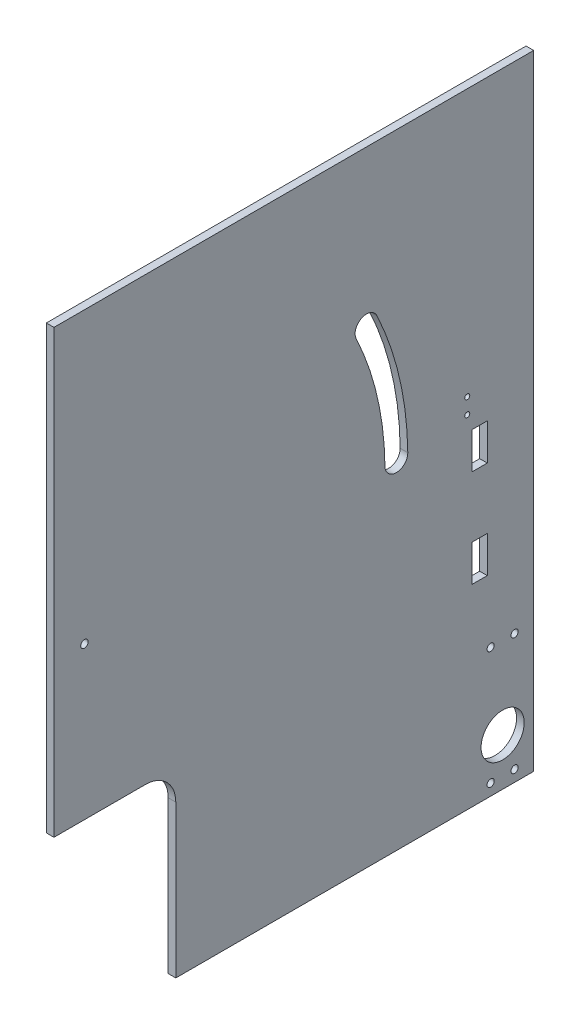
SolidWorks part; units mm, degrees
material "Acrylic (Medium-high impact)"
ref_plane "Front" through (0, 0, 0) normal (0, 0, 1) x (1, 0, 0)
ref_plane "Top" through (0, 0, 0) normal (0, 1, 0) x (1, 0, 0)
ref_plane "Right" through (0, 0, 0) normal (1, 0, 0) x (0, 0, -1)
sketch "Sketch1" plane through (0, 0, 0) normal (1, 0, 0) x (0, 0, -1)
  line L1 (-100.0125, 130.175) -> (100.0125, 130.175)
  line L2 (-100.0125, 130.175) -> (-100.0125, -130.175)
  line L3 (-100.0125, -130.175) -> (100.0125, -130.175)
  line L4 (100.0125, 130.175) -> (100.0125, -130.175)
  point P4 (-100.0125, 0)
  point P6 (0, 130.175)
  dimension "D1" = 260.35
  dimension "D2" = 200.025
extrude "Boss-Extrude1" add sketch "Sketch1" along normal blind 3.175
sketch "Sketch3" plane through (0, 0, 0) normal (-1, 0, 0) x (0, 0, 1)
  line L0 (-55.5625, 104.775) -> (77.7875, 104.775)
  line L1 (77.7875, 79.375) -> (-55.5625, 79.375)
  line L2 (-26.9875, 130.175) -> (-26.9875, -130.175) construction
  line L3 (-100.0125, 130.175) -> (100.0125, 130.175) construction
  line L4 (100.0125, -130.175) -> (-100.0125, -130.175) construction
  line L5 (100.0125, 130.175) -> (100.0125, -130.175) construction
  line L6 (-60.7375, 79.375) -> (-60.7375, 80.4772)
  line L12 (-55.5625, 92.075) -> (-68.2625, 92.075) construction
  arc A0 (77.7875, 104.775) -> (77.7875, 79.375) centre (77.7875, 92.075) cw
  arc A1 (-55.5625, 79.375) -> (-55.5625, 104.775) centre (-55.5625, 92.075) cw
  point P15 (90.4875, 92.075)
  dimension "D1" = 25.4
  dimension "D3" = 133.35
  dimension "D2" = 9.525
  dimension "D4" = 127
  dimension "D5" = 222.25
  dimension "D8" = 5.175
extrude "Cut-Extrude1" [suppressed] cut sketch "Sketch3" against normal through all contours A1 L1 A0 L0
sketch "Sketch6" plane through (3.175, 0, 0) normal (1, 0, 0) x (0, 0, -1)
  line L0 (117.5875, -88.265) -> (117.5875, -83.185)
  line L1 (139.5875, -83.185) -> (139.5875, -88.265)
  line L2 (111.5875, -103.765) -> (111.5875, -98.685)
  line L3 (114.5875, -103.765) -> (114.5875, -98.685)
  line L4 (111.5875, -72.765) -> (111.5875, -67.685)
  line L5 (114.5875, -72.765) -> (114.5875, -67.685)
  line L6 (128.5875, -83.185) -> (128.5875, -88.265) construction
  line L7 (145.5875, -103.765) -> (145.5875, -98.685)
  line L8 (142.5875, -103.765) -> (142.5875, -98.685)
  line L9 (142.5875, -72.765) -> (142.5875, -67.685)
  line L10 (145.5875, -72.765) -> (145.5875, -67.685)
  line L11 (-100.0125, 130.175) -> (-100.0125, -130.175) construction
  line L12 (-100.0125, -130.175) -> (100.0125, -130.175) construction
  arc A0 (117.5875, -88.265) -> (139.5875, -88.265) centre (128.5875, -88.265) ccw
  arc A1 (139.5875, -83.185) -> (117.5875, -83.185) centre (128.5875, -83.185) ccw
  arc A2 (111.5875, -103.765) -> (114.5875, -103.765) centre (113.0875, -103.765) ccw
  arc A3 (114.5875, -98.685) -> (111.5875, -98.685) centre (113.0875, -98.685) ccw
  arc A4 (111.5875, -72.765) -> (114.5875, -72.765) centre (113.0875, -72.765) ccw
  arc A5 (114.5875, -67.685) -> (111.5875, -67.685) centre (113.0875, -67.685) ccw
  arc A6 (145.5875, -103.765) -> (142.5875, -103.765) centre (144.0875, -103.765) cw
  arc A7 (142.5875, -98.685) -> (145.5875, -98.685) centre (144.0875, -98.685) cw
  arc A8 (145.5875, -72.765) -> (142.5875, -72.765) centre (144.0875, -72.765) cw
  arc A9 (142.5875, -67.685) -> (145.5875, -67.685) centre (144.0875, -67.685) cw
  circle A10 centre (113.0875, -69.36) radius 3.175
  circle A11 centre (144.0875, -69.36) radius 3.175
  circle A12 centre (113.0875, -102.09) radius 3.175
  circle A13 centre (144.0875, -102.09) radius 3.175
  point P37 (128.5875, -85.725)
  point P38 (139.5875, -85.725)
  dimension "D5" = 1.5
  dimension "D9" = 1.5
  dimension "D12" = 6.35
  dimension "D1" = 5.08
  dimension "D2" = 5.08
  dimension "D3" = 15.5
  dimension "D4" = 15.5
  dimension "D6" = 15.5
  dimension "D7" = 15.5
  dimension "D8" = 5.08
  dimension "D10" = 228.6
  dimension "D11" = 44.45
sketch "Sketch8" plane through (0, 0, 0) normal (-1, 0, 0) x (0, 0, 1)
  line L0 (100.0125, 130.175) -> (100.0125, -130.175) construction
  line L1 (100.0125, -130.175) -> (-100.0125, -130.175) construction
  line L3 (100.0125, -130.175) -> (-100.0125, -130.175) construction
  circle A0 centre (87.3125, 9.525) radius 1.55
  circle A5 centre (-72.3175, 18.925) radius 1.05
  circle A6 centre (-72.3175, 12.425) radius 1.05
  point P11 (-63.8175, 22.225)
  dimension "D1" = 3.1
  dimension "D15" = 3.3
  dimension "D8" = 2.1
  dimension "D2" = 12.7
  dimension "D3" = 139.7
  dimension "D6" = 151.13
  dimension "D7" = 152.4
  dimension "D9" = 6.5
  dimension "D12" = 8.5
extrude "Cut-Extrude7" cut sketch "Sketch8" against normal through all
sketch "Sketch9" plane through (0, 0, 0) normal (-1, 0, 0) x (0, 0, 1)
  line L0 (100.0125, 130.175) -> (100.0125, -130.175) construction
  line L1 (100.0125, -53.975) -> (49.2125, -53.975)
  line L2 (100.0125, -53.975) -> (100.0125, -130.175)
  line L3 (100.0125, -130.175) -> (49.2125, -130.175)
  line L4 (49.2125, -53.975) -> (49.2125, -130.175)
  line L5 (100.0125, -130.175) -> (-100.0125, -130.175) construction
  dimension "D1" = 50.8
  dimension "D2" = 76.2
extrude "Cut-Extrude8" cut sketch "Sketch9" against normal through all
fillet "Fillet1" radius 12.7 1 edges at (1.5875, -53.975, 49.2125)
sketch "Sketch10" plane through (0, 0, 0) normal (-1, 0, 0) x (0, 0, 1)
  line L4 (-42.8232, -130.175) -> (-42.8232, 6.325) construction
  line L5 (49.2125, -130.175) -> (-100.0125, -130.175) construction
  arc A9 (-28.2913, 69.3688) -> (-42.8232, 6.325) centre (87.3125, 9.525) ccw construction
  arc A10 (-34.6312, 67.0954) -> (-47.5281, 11.1443) centre (87.3125, 9.525) ccw
  arc A11 (-26.0179, 63.0289) -> (-38.0038, 11.03) centre (87.3125, 9.525) ccw
  arc A12 (-47.5281, 11.1443) -> (-38.0038, 11.03) centre (-42.766, 11.0872) ccw
  arc A13 (-34.6312, 67.0954) -> (-26.0179, 63.0289) centre (-30.3245, 65.0622) cw
  circle A14 centre (87.3125, 9.525) radius 125.3254 construction
  circle A15 centre (87.3125, 9.525) radius 130.175 construction
  circle A16 centre (87.3125, 9.525) radius 134.8504 construction
  point P23 (-28.2913, 69.3688)
  dimension "D1" = 4.7625
  dimension "D2" = 136.5
  dimension "D4" = 260.35
  dimension "D3" = 53.975
extrude "Cut-Extrude9" cut sketch "Sketch10" against normal through all
sketch "Sketch14" plane through (3.175, 0, 0) normal (1, 0, 0) x (0, 0, -1)
  line L0 (36.5125, -130.175) -> (36.5125, 130.175) construction
  line L5 (-49.2125, -130.175) -> (100.0125, -130.175) construction
  line L6 (100.0125, 130.175) -> (-100.0125, 130.175) construction
  line L7 (-100.0125, 130.175) -> (-100.0125, -53.975) construction
  line L14 (65.0875, -120.523) -> (65.0875, -126.873) construction
  circle A0 centre (-87.3125, 9.525) radius 186.3916 construction
  arc A1 (35.0388, -128.905) -> (41.3847, -122.7825) centre (35.0388, -122.555) ccw construction
  circle A2 centre (65.0875, -126.873) radius 1.5
  circle A3 centre (65.0875, -120.523) radius 1.5
  dimension "D6" = 3
  dimension "D7" = 6.35
  dimension "D1" = 136.525
  dimension "D8" = 3.302
  dimension "D9" = 28.575
extrude "Cut-Extrude11" [suppressed] cut sketch "Sketch14" against normal through all
sketch "Sketch15" plane through (3.175, 0, 0) normal (1, 0, 0) x (0, 0, -1)
  line L1 (74.3175, 6.075) -> (80.6675, 6.075)
  line L2 (74.3175, 6.075) -> (74.3175, -9.165)
  line L3 (74.3175, -9.165) -> (80.6675, -9.165)
  line L4 (80.6675, 6.075) -> (80.6675, -9.165)
  line L11 (74.3175, -34.565) -> (80.6675, -34.565)
  line L12 (74.3175, -34.565) -> (74.3175, -49.805)
  line L13 (74.3175, -49.805) -> (80.6675, -49.805)
  line L14 (80.6675, -34.565) -> (80.6675, -49.805)
  circle A0 centre (72.3175, 12.425) radius 1.05 construction
  dimension "D4" = 2
  dimension "D1" = 6.35
  dimension "D2" = 15.24
  dimension "D3" = 25.4
  dimension "D5" = 6.35
extrude "Cut-Extrude12" cut sketch "Sketch15" against normal through all
sketch "Sketch16" plane through (3.175, 0, 0) normal (1, 0, 0) x (0, 0, -1)
  line L0 (82.075, -76.4125) -> (92.075, -76.4125) construction
  line L1 (82.075, -76.4125) -> (82.075, -125.4125) construction
  line L2 (92.075, -76.4125) -> (92.075, -125.4125) construction
  line L3 (82.075, -125.4125) -> (92.075, -125.4125) construction
  line L4 (100.0125, -130.175) -> (100.0125, 130.175) construction
  line L6 (87.075, -125.4125) -> (87.075, -110.5625) construction
  line L7 (87.075, -119.5625) -> (68.66, -119.5625) construction
  line L9 (-49.2125, -130.175) -> (100.0125, -130.175) construction
  circle A0 centre (82.075, -125.4125) radius 1.5
  circle A1 centre (82.075, -76.4125) radius 1.5
  circle A2 centre (92.075, -125.4125) radius 1.5
  circle A3 centre (92.075, -76.4125) radius 1.5
  circle A4 centre (87.075, -110.5625) radius 9
  dimension "D1" = 3
  dimension "D7" = 18
  dimension "D2" = 10
  dimension "D3" = 49
  dimension "D4" = 14.85
  dimension "D5" = 7.9375
  dimension "D6" = 4.7625
extrude "Cut-Extrude13" cut sketch "Sketch16" against normal through all
equation "\"bottomThickness\"= .220in"
equation "\"wallThickness\"= .125in"
equation "\"D1@Boss-Extrude1\"=\"wallThickness\""
